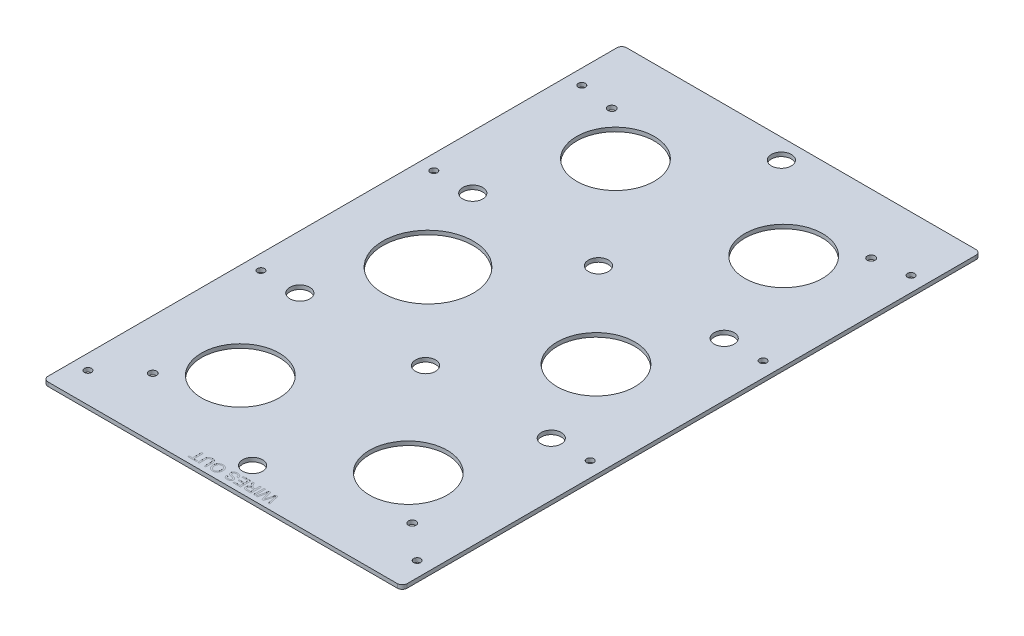
SolidWorks part; units mm, degrees
ref_plane "Front" through (0, 0, 0) normal (0, 0, 1) x (1, 0, 0)
ref_plane "Top" through (0, 0, 0) normal (0, 1, 0) x (1, 0, 0)
ref_plane "Right" through (0, 0, 0) normal (1, 0, 0) x (0, 0, -1)
sketch "Sketch1" plane through (0, 0, 0) normal (0, 1, 0) x (1, 0, 0)
  line L0 (456.579, -102.8629) -> (456.452, -102.8629) construction
  line L1 (423.5718, 200.6671) -> (645.8218, 200.6671)
  line L2 (420.3968, 197.4921) -> (420.3968, -164.4579)
  line L3 (423.5718, -167.6329) -> (645.8218, -167.6329)
  line L4 (648.9968, 197.4921) -> (648.9968, -164.4579)
  line L5 (420.3968, 200.6671) -> (648.9968, -167.6329) construction
  line L6 (420.3968, -167.6329) -> (648.9968, 200.6671) construction
  line L7 (461.583, 36.5814) -> (500.7749, -3.4186) construction
  line L8 (561.6843, -167.6329) -> (645.8218, -167.6329) construction
  line L9 (648.9968, -164.4579) -> (648.9968, 197.4921) construction
  circle A0 centre (588.2146, -102.9915) radius 24.727
  circle A1 centre (588.2146, 16.4528) radius 24.727
  circle A2 centre (481.179, -102.8629) radius 24.727
  circle A4 centre (481.179, 135.8971) radius 24.727
  circle A5 centre (588.2146, 135.8971) radius 24.727
  arc A6 (486.1357, -126.9584) -> (483.7873, -78.4016) centre (481.179, -102.8629) ccw construction
  arc A7 (486.1357, -126.9584) -> (476.2222, -78.7675) centre (481.179, -102.8629) ccw construction
  arc A8 (648.9968, 197.4921) -> (645.8218, 200.6671) centre (645.8218, 197.4921) ccw
  arc A9 (420.3968, 197.4921) -> (423.5718, 200.6671) centre (423.5718, 197.4921) cw
  arc A10 (420.3968, -164.4579) -> (423.5718, -167.6329) centre (423.5718, -164.4579) ccw
  arc A11 (645.8218, -167.6329) -> (648.9968, -164.4579) centre (645.8218, -164.4579) ccw
  circle A12 centre (481.179, 16.5814) radius 28.7693
  circle A13 centre (454.6868, -38.512) radius 2.2479 construction
  circle A14 centre (454.6868, -38.512) radius 2.2479 construction
  circle A15 centre (534.6968, -38.5162) radius 2.2479 construction
  circle A16 centre (534.6968, -38.5162) radius 2.2479 construction
  circle A17 centre (614.7068, -38.512) radius 2.2479 construction
  circle A18 centre (614.7068, -38.512) radius 2.2479 construction
  circle A19 centre (614.7068, 71.5462) radius 2.2479 construction
  circle A20 centre (614.7068, 71.5462) radius 2.2479 construction
  circle A21 centre (534.6968, 71.5504) radius 2.2479 construction
  circle A22 centre (534.6968, 71.5504) radius 2.2479 construction
  circle A23 centre (454.6868, 71.5462) radius 2.2479 construction
  circle A24 centre (454.6868, 71.5462) radius 2.2479 construction
  circle A25 centre (534.6968, 187.9671) radius 2.2479 construction
  circle A26 centre (534.6968, 187.9671) radius 2.2479 construction
  circle A27 centre (534.6968, -148.5829) radius 2.2479 construction
  circle A28 centre (534.6968, -148.5829) radius 2.2479 construction
  circle A29 centre (534.6968, -148.5829) radius 6.35
  circle A30 centre (614.7068, -38.512) radius 6.35
  circle A31 centre (534.6968, -38.5162) radius 6.35
  circle A32 centre (454.6868, -38.512) radius 6.35
  circle A33 centre (614.7068, 71.5462) radius 6.35
  circle A34 centre (534.6968, 71.5504) radius 6.35
  circle A35 centre (454.6868, 71.5462) radius 6.35
  circle A36 centre (534.6968, 187.9671) radius 6.35
  circle A37 centre (617.2468, 162.5671) radius 2.4574 construction
  circle A38 centre (617.2468, 162.5671) radius 2.4575
  circle A39 centre (452.1468, 162.5671) radius 2.4574 construction
  circle A40 centre (452.1468, 162.5671) radius 2.4575
  circle A41 centre (452.1468, -129.5329) radius 2.4575 construction
  circle A42 centre (452.1468, -129.5329) radius 2.4575
  circle A43 centre (617.2468, -129.5329) radius 2.4575 construction
  circle A44 centre (617.2468, -129.5329) radius 2.4575
  circle A45 centre (429.9218, 165.7421) radius 2.2479 construction
  circle A46 centre (429.9218, 165.7421) radius 2.2479
  circle A47 centre (429.9218, 71.5504) radius 2.2479 construction
  circle A48 centre (429.9218, 71.5504) radius 2.2479
  circle A49 centre (639.4718, 165.7421) radius 2.2479 construction
  circle A50 centre (639.4718, 165.7421) radius 2.2479
  circle A51 centre (639.4718, 71.5504) radius 2.2479 construction
  circle A52 centre (639.4718, 71.5504) radius 2.2479
  circle A53 centre (639.4718, -38.5162) radius 2.2479 construction
  circle A54 centre (639.4718, -38.5162) radius 2.2479
  circle A55 centre (429.9218, -38.5162) radius 2.2479 construction
  circle A56 centre (429.9218, -38.5162) radius 2.2479
  circle A57 centre (429.9218, -148.5829) radius 2.2479 construction
  circle A58 centre (429.9218, -148.5829) radius 2.2479
  circle A59 centre (639.4718, -148.5829) radius 2.2479 construction
  circle A60 centre (639.4718, -148.5829) radius 2.2479
  point P0 (534.6968, 16.5171)
  dimension "D3" = 0.127
  dimension "D4" = 3.175
  dimension "D5" = 12.7
  dimension "D1" = 228.6
  dimension "D2" = 368.3
extrude "Boss-Extrude1" add sketch "Sketch1" along normal blind 2.54
sketch "Sketch2" plane through (0, 2.54, 0) normal (0, 1, 0) x (1, 0, 0)
  line L0 (561.4894, -157.6329) -> (561.4894, -167.6329) construction
  line L2 (561.4894, -157.6329) -> (510.6894, -157.6329) construction
  line L3 (423.5718, -167.6329) -> (645.8218, -167.6329) construction
  line L4 (648.9968, -164.4579) -> (648.9968, 197.4921) construction
  text T0 "WIRES OUT" font "Arial" height in points 26
  dimension "D1" = 10
  dimension "D2" = 50.8
  dimension "D3" = 87.5074
extrude "Cut-Extrude2" cut sketch "Sketch2" against normal blind 0.0254
